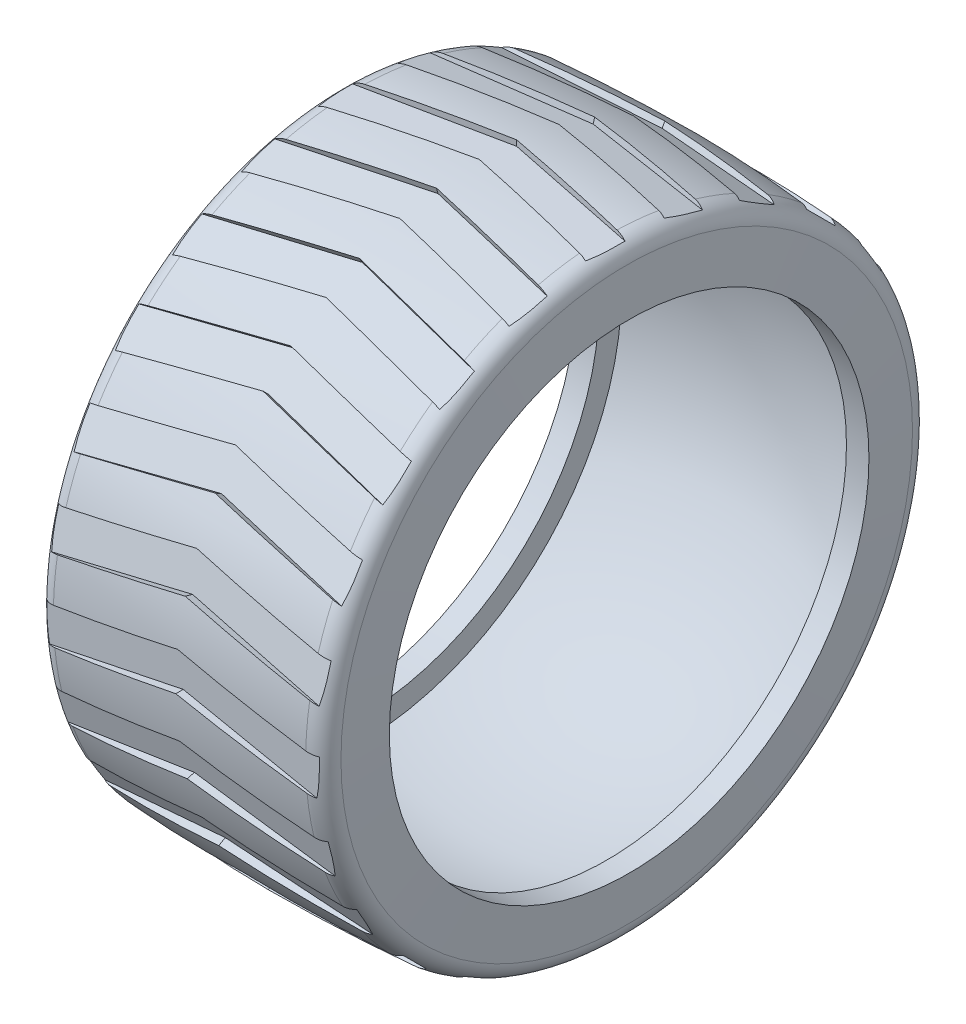
SolidWorks part; units mm, degrees
ref_plane "Ebene vorne" through (0, 0, 0) normal (0, 0, 1) x (1, 0, 0)
ref_plane "Ebene oben" through (0, 0, 0) normal (0, 1, 0) x (1, 0, 0)
ref_plane "Ebene rechts" through (0, 0, 0) normal (1, 0, 0) x (0, 0, -1)
ref_axis "Achse1" through (-20.3528, 0, 0) along (1, 0, 0)
sketch "Skizze2" plane through (0, 0, 0) normal (0, 0, 1) x (1, 0, 0)
  line L0 (-16.5, 35) -> (-16.5, 32)
  line L1 (0, 0) -> (24.8739, 0) construction
  line L2 (0, 37.5) -> (0, 0) construction
  line L3 (-16.5, 32) -> (-19.5, 32)
  line L4 (-19.5, 32) -> (-19.5, 41)
  line L5 (-19.5, 41) -> (19.5, 41)
  line L6 (19.5, 32) -> (19.5, 41)
  line L7 (16.5, 32) -> (19.5, 32)
  line L8 (16.5, 35) -> (16.5, 32)
  arc A0 (-16.5, 35) -> (16.5, 35) centre (0, -18.2) cw
  point P3 (0, 37.5)
  dimension "D2" = 75
  dimension "D1" = 70
  dimension "D3" = 33
  dimension "D4" = 3
  dimension "D5" = 82
  dimension "D6" = 3
revolve "Rotation1" add sketch "Skizze2" angle 360 about L1
ref_plane "Ebene1" through (0, 0, 41) normal (0, 0, 1) x (1, 0, 0)
sketch "Skizze3" plane through (0, 0, 41) normal (0, 0, 1) x (1, 0, 0)
  line L0 (-19.5, 0.5) -> (0, 4.5)
  line L1 (-19.5, 41) -> (-19.5, -41) construction
  line L2 (0, 4.5) -> (19.5, 0.5)
  line L3 (19.5, -41) -> (19.5, 41) construction
  line L4 (19.5, 0.5) -> (19.5, -4.5)
  line L5 (19.5, -4.5) -> (0, -0.5)
  line L6 (0, -0.5) -> (-19.5, -4.5)
  line L7 (-19.5, -4.5) -> (-19.5, 0.5)
  line L8 (0, 4.5) -> (0, 0) construction
  line L9 (-19.5, -4.5) -> (19.5, -4.5) construction
  line L10 (-19.5, 4.5) -> (18.5, 4.5) construction
  line L11 (-19.5, 0) -> (19.5, 0) construction
  dimension "D1" = 5
  dimension "D2" = 9
extrude "Schnitt-Linear austragen2" cut sketch "Skizze3" against normal blind 1
pattern_circular "Kreismuster6" count 24 over 360 about axis through (-20.3528, 0, 0) along (1, 0, 0) of "Schnitt-Linear austragen2"
sketch "Skizze4" plane through (0, 0, 0) normal (0, 0, 1) x (1, 0, 0)
  line L0 (0, 0) -> (0, 40.997) construction
  line L1 (-19.1786, 38.1322) -> (-19.5, 32)
  line L3 (-18.5, 0) -> (18.5, 0) construction
  line L4 (-20.5, 32) -> (-20.5, 41.997)
  line L5 (-19.5, 32) -> (-20.5, 32)
  line L6 (-20.5, 41.997) -> (20.5, 41.997)
  line L7 (20.5, 41.997) -> (20.5, 32)
  line L8 (19.5, 32) -> (20.5, 32)
  line L10 (19.1786, 38.1322) -> (19.5, 32)
  arc A0 (-16.8305, 40.497) -> (16.8305, 40.497) centre (0, -242.5174) cw
  arc A1 (-16.8305, 40.497) -> (-19.1786, 38.1322) centre (-16.6821, 38.0014) ccw
  arc A2 (16.8305, 40.497) -> (19.1786, 38.1322) centre (16.6821, 38.0014) cw
  dimension "D2" = 3
  dimension "D5" = 2.5
  dimension "D1" = 0.5
  dimension "D3" = 1
  dimension "D4" = 1
revolve "Schnitt-Rotation5" cut sketch "Skizze4" angle 360 about L3
